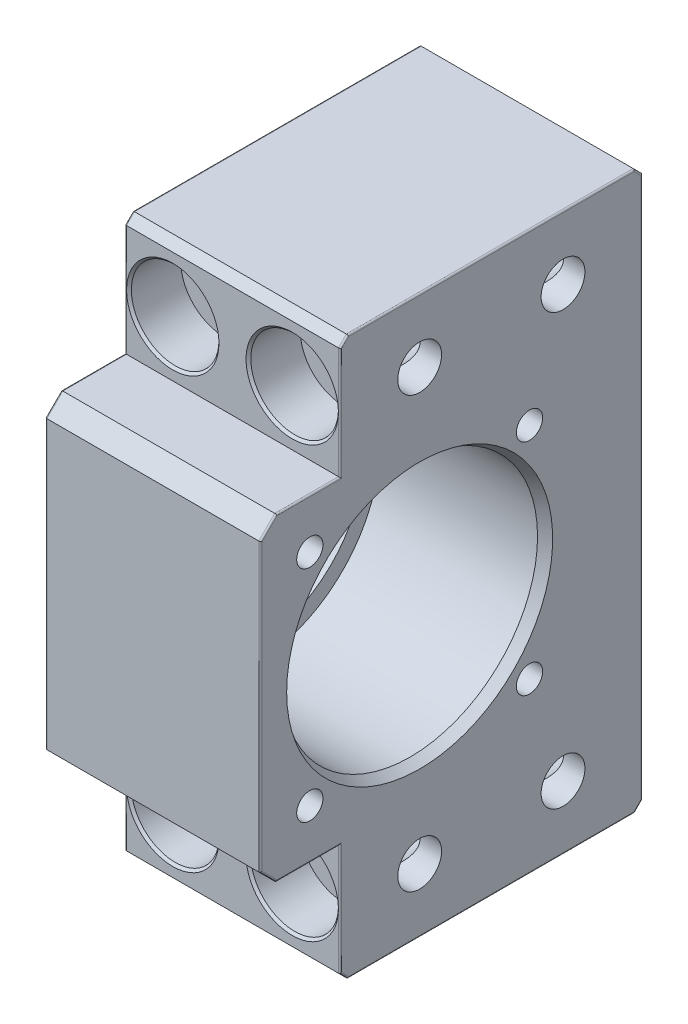
SolidWorks part; units mm, degrees
material "6063-T1"
ref_plane "Front Plane" through (0, 0, 0) normal (0, 0, 1) x (1, 0, 0)
ref_plane "Top Plane" through (0, 0, 0) normal (0, 1, 0) x (1, 0, 0)
ref_plane "Right Plane" through (0, 0, 0) normal (1, 0, 0) x (0, 0, -1)
ref_plane "Plane1" through (-13.5, 0, 0) normal (-1, 0, 0) x (0, -1, 0)
sketch "Sketch1" plane through (-13.5, 0, 0) normal (-1, 0, 0) x (0, -1, 0)
  line L0 (35, 24) -> (-35, 24)
  line L1 (-35, 24) -> (-35, -24)
  line L2 (-35, -24) -> (35, -24)
  line L3 (35, -24) -> (35, 24)
  line L4 (0, -1000) -> (0, 49000) construction
  line L5 (-1000, 0) -> (49000, 0) construction
  dimension "D1" = 48
  dimension "D2" = 70
extrude "Boss-Extrude1" add sketch "Sketch1" against normal blind 27
sketch "Sketch2" plane through (13.5, 0, 0) normal (1, 0, 0) x (0, 0, -1)
  line L0 (-24, 35) -> (-24, 20)
  line L1 (-24, 20) -> (-14, 20)
  line L2 (-14, 20) -> (-14, 35)
  line L3 (-14, 35) -> (-24, 35)
  line L5 (-24, -35) -> (-14, -35)
  line L6 (-24, -35) -> (-24, -20)
  line L7 (-24, -20) -> (-14, -20)
  line L8 (-14, -35) -> (-14, -20)
  dimension "D1" = 10
  dimension "D2" = 15
extrude "Cut-Extrude1" cut sketch "Sketch2" against normal through all
hole_wizard "Hole1" positions "Sketch5" profile "Sketch4" legacy end condition through all
sketch "Sketch5" plane through (13.5, 0, 0) normal (1, 0, 0) x (0, 0, -1)
  line L1 (24, 35) -> (24, -35) construction
  line L2 (-1000, 0) -> (49000, 0) construction
  point P0 (-4, 0)
  dimension "D1" = 28
sketch "Sketch4" plane through (13.5, 0, 4) normal (0, 1, 0) x (0, 0, -1)
  line L0 (0, 0) -> (0, 27)
  line L1 (0, 27) -> (14, 27)
  line L2 (14, 27) -> (14, 21)
  line L3 (14, 21) -> (16, 21)
  line L4 (16, 21) -> (16, 0)
  line L5 (16, 0) -> (0, 0)
  line L6 (0, 110) -> (0, -10) construction
  dimension "Diameter" = 28
  dimension "Depth" = 27
  dimension "C-Bore Diameter" = 32
  dimension "C-Bore Depth" = 21
hole_wizard "Ø5.5 (5.5) Diameter Hole1" positions "Sketch7" profile "Sketch6" hole size "Ø5.5" standard "ANSI Metric" end condition through all
sketch "Sketch7" plane through (-13.5, 0, 0) normal (-1, 0, 0) x (0, 0, 1)
  line L0 (-1000, 0) -> (49000, 0) construction
  line L1 (0, -1000) -> (0, 49000) construction
  line L2 (-24, 35) -> (-24, -35) construction
  line L3 (14, 35) -> (-24, 35) construction
  line L4 (-24, -35) -> (14, -35) construction
  point P0 (4, 27)
  point P1 (-14, 27)
  point P16 (4, -27)
  point P18 (-14, -27)
  dimension "D1" = 18
  dimension "D2" = 10
  dimension "D3" = 8
  dimension "D4" = 10
  dimension "D5" = 8
  dimension "D6" = 54
sketch "Sketch6" plane through (-13.5, 27, 4) normal (0, 1, 0) x (0, 0, 1)
  line L0 (0, 0) -> (0, 27)
  line L1 (0, 27) -> (2.75, 27)
  line L2 (2.75, 27) -> (2.75, 0)
  line L5 (2.75, 0) -> (0, 0)
  line L11 (0, -6.35) -> (0, 107.95) construction
  dimension "Thru Hole Dia." = 5.5
  dimension "Thru Hole Depth" = 27
hole_wizard "CBORE for M6 Hex Socket Thin Head Cap Screw1" positions "Sketch9" profile "Sketch8" counterbore size "M6" standard "DIN" end condition through all
sketch "Sketch9" plane through (0, 0, 14) normal (0, 0, 1) x (1, 0, 0)
  line L0 (-1000, 0) -> (49000, 0) construction
  line L1 (0, -1000) -> (0, 49000) construction
  point P0 (-7.5, -27)
  point P1 (7.5, -27)
  point P2 (7.5, 27)
  point P3 (-7.5, 27)
  dimension "D1" = 54
  dimension "D2" = 15
sketch "Sketch8" plane through (-7.5, -27, 14) normal (1, 0, 0) x (0, -1, 0)
  line L0 (0, 0) -> (0, 38)
  line L1 (3.3, 37.7) -> (3.6, 38)
  line L2 (5.5, 6.5) -> (3.3, 6.5)
  line L3 (3.3, 6.5) -> (3.3, 37.7)
  line L5 (5.5, 6.5) -> (5.5, 0.3)
  line L6 (5.5, 0.3) -> (5.8, 0)
  line L7 (5.8, 0) -> (0, 0)
  line L8 (-5.5, 0.3) -> (-5.8, 0) construction
  line L11 (0, -6.35) -> (0, 107.95) construction
  line L12 (3.6, 38) -> (0, 38)
  line L13 (-3.3, 37.7) -> (-3.6, 38) construction
  dimension "Thru Hole Dia." = 6.6
  dimension "Thru Hole Depth" = 38
  dimension "C'Bore Dia." = 11
  dimension "C'Bore Depth" = 6.5
  dimension "Near C'Sink Dia." = 11.6
  dimension "Near C'Sink Angle" = 90
  dimension "Far C'Sink Dia." = 7.2
  dimension "Far C'Sink Angle" = 90
hole_wizard "Tap Drill for M4x0.7 Tap1" positions "Sketch16" profile "Sketch15" hole size "M4x0.7" standard "ANSI Metric"
sketch "Sketch16" plane through (13.5, 0, 0) normal (-1, 0, 0) x (0, 0, 1)
  line L0 (4, 0) -> (-35351.3391, 35355.3391) construction
  line L1 (-18.3773, -22.3773) -> (35336.9617, 35332.9617) construction
  line L2 (4, -1000) -> (4, 49000) construction
  circle A0 centre (4, 0) radius 19.5 construction
  point P5 (-9.7886, 13.7886)
  point P6 (17.7886, 13.7886)
  point P7 (17.7886, -13.7886)
  point P15 (-9.7886, -13.7886)
  dimension "D1" = 39
  dimension "D2" = 90
  dimension "D3" = 45
sketch "Sketch15" plane through (13.5, 13.7886, -9.7886) normal (0, 1, 0) x (0, 0, -1)
  line L0 (0, 0) -> (0, 12.8589)
  line L1 (0, 12.8589) -> (1.65, 12)
  line L2 (1.65, 12) -> (1.65, 0)
  line L5 (1.65, 0) -> (0, 0)
  line L10 (0, 12.8589) -> (-1.65, 12) construction
  line L11 (0, -6.35) -> (0, 107.95) construction
  dimension "Hole Dia." = 3.3
  dimension "Hole Depth" = 12
  dimension "Drill Angle" = 125
cosmetic thread "Cosmetic Thread1" parameters "D2"=4
cosmetic thread "Cosmetic Thread2" parameters "D2"=4
cosmetic thread "Cosmetic Thread3" parameters "D2"=4
cosmetic thread "Cosmetic Thread4" parameters "D2"=4
chamfer "Chamfer1" distance 1 angle 45 4 edges at (0, -35, -24) (0, 35, -24) (0, 35, 14) (0, -35, 14)
chamfer "Chamfer3" distance 2 angle 45 2 edges at (0, 20, 24) (0, -20, 24)
chamfer "Chamfer2" distance 0.7 distance2 1.2 1 edges at (13.5, 0, -12) first distance on face at (13.5, 13.7886, -11.4386)
chamfer "Chamfer4" distance 0.5 angle 45 1 edges at (-13.5, 0, -10)
fillet "Fillet1" radius 0.2 28 edges at (13.5, 35, -5) (13.5, 34.5, 13.5) (13.5, 27, 14) (13.5, 20, 18) (-13.5, 34.5, -23.5) (-13.5, 0, -24) (-13.5, -34.5, -23.5) (-13.5, -35, -5) (-13.5, -34.5, 13.5) (-13.5, 35, -5) (-13.5, 34.5, 13.5) (-13.5, 19, 23) (-13.5, 20, 18) (-13.5, 27, 14) (-13.5, -27, 14) (-13.5, -20, 18) (-13.5, -19, 23) (-13.5, 0, 24) (13.5, 19, 23) (13.5, 0, 24) (13.5, -19, 23) (13.5, -20, 18) (13.5, -27, 14) (13.5, -34.5, 13.5) (13.5, -35, -5) (13.5, -34.5, -23.5) (13.5, 0, -24) (13.5, 34.5, -23.5)
